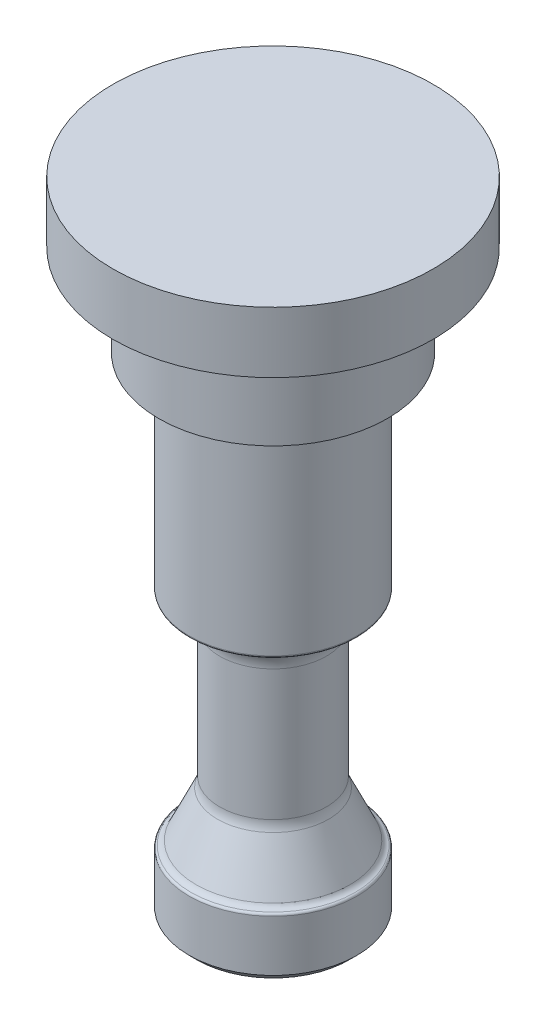
SolidWorks part; units mm, degrees
ref_plane "Front Plane" through (0, 0, 0) normal (0, 0, 1) x (1, 0, 0)
ref_plane "Top Plane" through (0, 0, 0) normal (0, 1, 0) x (1, 0, 0)
ref_plane "Right Plane" through (0, 0, 0) normal (1, 0, 0) x (0, 0, -1)
sketch "Sketch1" plane through (0, 0, 0) normal (0, 1, 0) x (1, 0, 0)
  circle A0 centre (0, 0) radius 8.7312
  dimension "D1" = 17.4625
extrude "main" add sketch "Sketch1" along normal blind 50.8
chamfer "Chamfer1" distance 0.7937 1 edges at (0, 0, 8.7312)
sketch "Sketch2" plane through (0, 0, 0) normal (1, 0, 0) x (0, 0, -1)
  line L0 (8.7312, 0.7938) -> (8.7312, 50.8) construction
  line L1 (-8.7312, 50.8) -> (-8.7312, 0.7938) construction
  line L2 (8.7312, 50.8) -> (-8.7312, 50.8) construction
  line L3 (8.7312, 0.7938) -> (8.7312, 50.8)
  line L4 (-8.7312, 50.8) -> (-8.7312, 0.7938)
  line L5 (8.7312, 50.8) -> (-8.7312, 50.8)
  line L6 (-5.7794, 11.5959) -> (-8.0119, 6.8083)
  line L8 (-8.7312, 6.35) -> (-8.7312, 29.3687)
  line L10 (-5.5562, 12.6023) -> (-5.5562, 26.1937)
  line L11 (-7.9375, 0) -> (7.9375, 0) construction
  arc A0 (-8.7312, 29.3687) -> (-5.5562, 26.1937) centre (-8.7312, 26.1937) cw
  arc A2 (-5.5562, 12.6023) -> (-5.7794, 11.5959) centre (-7.9375, 12.6023) cw
  arc A4 (-8.7312, 6.35) -> (-8.0119, 6.8083) centre (-8.7312, 7.1437) ccw
  point P4 (0, 0)
  point P6 (0, 0)
  point P12 (0, 0)
  point P14 (0, 0)
  point P17 (0, 0)
  point P18 (0, 0)
  point P19 (0, 0)
  point P20 (0, 0)
  point P21 (0, 0)
  point P22 (0, 0)
  point P23 (0, 0)
  point P24 (0, 0)
  point P25 (0, 0)
  point P26 (0, 0)
  point P27 (0, 0)
  point P28 (0, 0)
  point P29 (0, 0)
  point P30 (0, 0)
  dimension "D4" = 23.0187
  dimension "D5" = 6.2523
  dimension "D6" = 3.175
  dimension "D1" = 3.175
  dimension "D2" = 2.3812
  dimension "D3" = 0.7937
  dimension "D7" = 6.35
  dimension "D8" = 25
ref_axis "Axis1" through (0, 50.8, 0) along (0, -1, 0)
revolve "ball_channel" cut sketch "Sketch2" angle 360 about axis through (0, 50.8, 0) along (0, -1, 0)
fillet "Fillet1" radius 0.254 3 edges at (0, 29.3687, 8.7312) (0, 50.8, 8.7312) (0, 6.35, 8.7312)
sketch "Sketch6" plane through (0, 50.8, 0) normal (0, 1, 0) x (1, 0, 0)
  circle A0 centre (0, 0) radius 11.9062
  dimension "D1" = 23.8125
extrude "spring_stabilizer" add sketch "Sketch6" along normal blind 9.525
sketch "Sketch3" plane through (0, 60.325, 0) normal (0, 1, 0) x (1, 0, 0)
  circle A0 centre (0, 0) radius 16.6687
  circle A3 centre (0, 0) radius 11.9062 construction
  circle A4 centre (0, 0) radius 11.9062
  circle M5 centre (0, 0) radius 11.9062
  dimension "D1" = 4.7625
extrude "top_cap" add sketch "Sketch3" along normal blind 6.35 contours A0 M5 | M5 region at (-16.1973, 60.325, 0) region at (0, 60.325, 0)
fillet "Fillet2" radius 1.27 1 edges at (0, 60.325, 11.9062)
sketch "Sketch4" [suppressed] plane through (0, 0, 0) normal (0, -1, 0) x (1, 0, 0)
  line L0 (-2.7079, 5.0327) -> (2.7079, 5.0327)
  line L1 (-2.7079, -5.0327) -> (2.7079, -5.0327)
  circle A0 centre (0, 0) radius 5.715 construction
  circle A1 centre (0, 0) radius 5.715
  circle A2 centre (0, 0) radius 5.0327 construction
  circle A3 centre (0, 0) radius 5.0327
  circle M3 centre (0, 0) radius 4.9213
  dimension "D1" = 5.4159
sketch "Sketch7" plane through (0, 0, 0) normal (0, -1, 0) x (1, 0, 0)
  circle A1 centre (0, 0) radius 2.3812
  dimension "D1" = 4.7625
extrude "Cut-Extrude1" cut sketch "Sketch7" against normal blind 19.05
ref_point "Point1"
extrude "spring_atchmnt_flat" [suppressed] cut sketch "Sketch4" against normal up to vertex contours L0 M3 | L1 M3
sketch "Sketch5" [suppressed] plane through (0, 0, 5.0327) normal (0, 0, 1) x (1, 0, 0)
  line L1 (-2.7079, 6.9053) -> (-2.7079, 0.7937) construction
  circle A0 centre (0, 3.8495) radius 1.5875
  point P7 (-2.7079, 3.8495)
  dimension "D1" = 3.175
extrude "spring_atchmnt_hole" [suppressed] cut sketch "Sketch5" against normal through all
